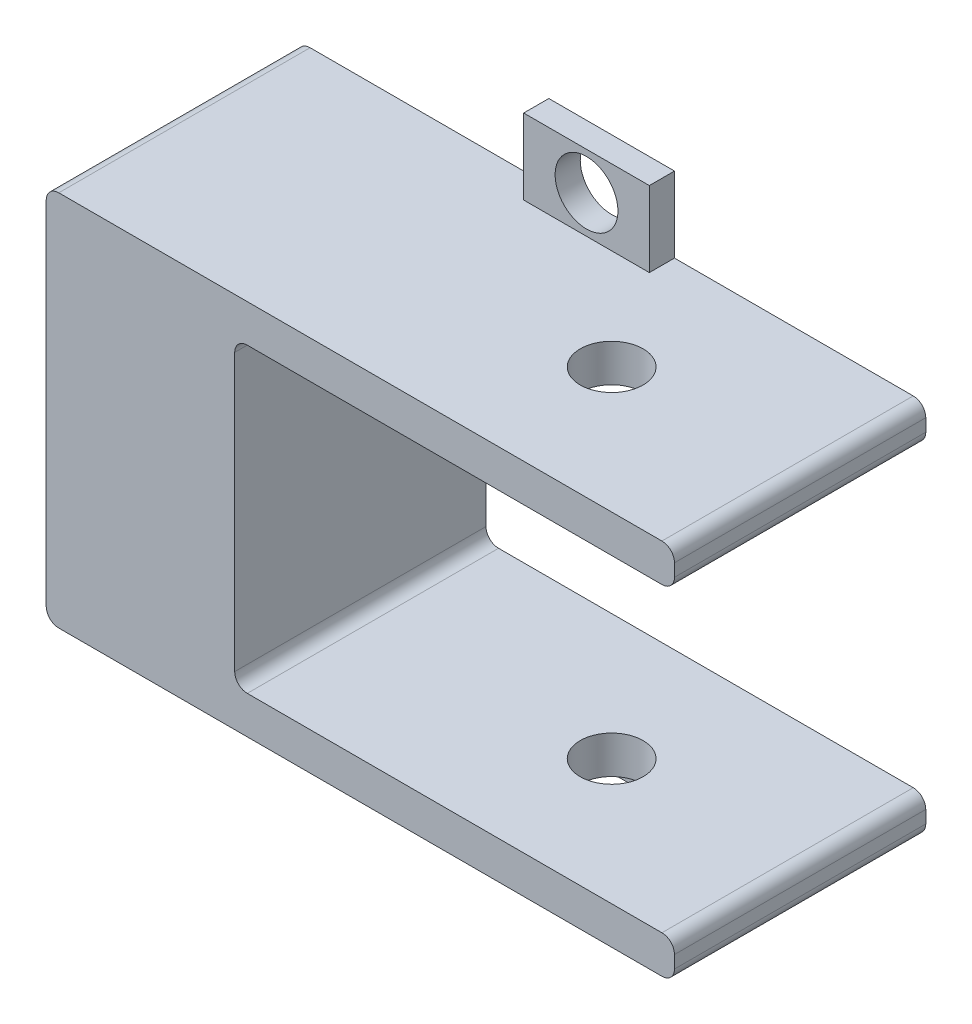
SolidWorks part; units mm, degrees
ref_plane "Front Plane" through (0, 0, 0) normal (0, 0, 1) x (1, 0, 0)
ref_plane "Top Plane" through (0, 0, 0) normal (0, 1, 0) x (1, 0, 0)
ref_plane "Right Plane" through (0, 0, 0) normal (1, 0, 0) x (0, 0, -1)
sketch "Sketch1" plane through (0, 0, 0) normal (0, 0, 1) x (1, 0, 0)
  line L1 (0, 0) -> (63.5, 0)
  line L2 (0, 0) -> (0, 38.1)
  line L3 (0, 38.1) -> (63.5, 38.1)
  line L4 (63.5, 0) -> (63.5, 38.1)
  dimension "D1" = 38.1
  dimension "D2" = 63.5
extrude "Boss-Extrude1" add sketch "Sketch1" along normal blind 25.4
sketch "Sketch3" plane through (0, 0, 0) normal (0, 0, -1) x (-1, 0, 0)
  line L0 (-63.5, 0) -> (-63.5, 38.1) construction
  line L1 (-63.5, 34.29) -> (-19.05, 34.29)
  line L2 (-63.5, 34.29) -> (-63.5, 3.81)
  line L3 (-63.5, 3.81) -> (-19.05, 3.81)
  line L4 (-19.05, 34.29) -> (-19.05, 3.81)
  line L9 (0, 0) -> (-63.5, 0) construction
  line L10 (-63.5, 38.1) -> (0, 38.1) construction
  dimension "D1" = 3.81
  dimension "D2" = 3.81
  dimension "D3" = 44.45
extrude "Cut-Extrude1" cut sketch "Sketch3" against normal blind 38.1
sketch "Sketch5" plane through (0, 0, 0) normal (0, -1, 0) x (1, 0, 0)
  line L0 (0, 0) -> (63.5, 0) construction
  circle A0 centre (44.45, 12.7) radius 3.175
  dimension "D1" = 6.35
  dimension "D2" = 12.7
  dimension "D3" = 19.05
extrude "Cut-Extrude2" cut sketch "Sketch5" against normal blind 76.2
fillet "Fillet3" radius 1.27 8 edges at (0, 38.1, 12.7) (0, 0, 12.7) (19.05, 3.81, 12.7) (19.05, 34.29, 12.7) (63.5, 3.81, 12.7) (63.5, 38.1, 12.7) (63.5, 34.29, 12.7) (63.5, 0, 12.7)
sketch "Sketch6" plane through (0, 38.1, 0) normal (0, 1, 0) x (1, 0, 0)
  line L5 (1.27, -25.4) -> (62.23, -25.4) construction
  line L6 (1.27, -22.86) -> (25.4, -22.86) construction
  line L7 (25.4, -25.4) -> (38.1, -25.4)
  line L8 (25.4, -25.4) -> (25.4, -22.86)
  line L9 (25.4, -22.86) -> (38.1, -22.86)
  line L10 (38.1, -25.4) -> (38.1, -22.86)
  line L11 (1.27, 0) -> (1.27, -25.4) construction
  line L12 (1.27, 0) -> (62.23, 0) construction
  dimension "D1" = 2.54
  dimension "D2" = 12.7
  dimension "D3" = 24.13
  dimension "D4" = 60.96
sketch "Sketch7" plane through (0, 0, 0) normal (0, -1, 0) x (1, 0, 0)
  line L0 (62.23, 22.86) -> (38.1, 22.86) construction
  line L1 (62.23, 0) -> (62.23, 25.4) construction
  line L2 (1.27, 25.4) -> (62.23, 25.4) construction
  line L3 (38.1, 22.86) -> (25.4, 22.86)
  line L4 (38.1, 22.86) -> (38.1, 25.4)
  line L5 (38.1, 25.4) -> (25.4, 25.4)
  line L6 (25.4, 22.86) -> (25.4, 25.4)
  dimension "D1" = 24.13
  dimension "D2" = 12.7
  dimension "D3" = 2.54
sketch "Sketch10" plane through (0, 0, 0) normal (0, -1, 0) x (1, 0, 0)
  line L0 (62.23, 2.54) -> (38.1, 2.54) construction
  line L1 (62.23, 0) -> (62.23, 25.4) construction
  line L2 (1.27, 0) -> (62.23, 0) construction
  line L3 (38.1, 2.54) -> (25.4, 2.54)
  line L4 (38.1, 2.54) -> (38.1, 0)
  line L5 (38.1, 0) -> (25.4, 0)
  line L6 (25.4, 2.54) -> (25.4, 0)
  dimension "D1" = 24.13
  dimension "D2" = 12.7
  dimension "D3" = 2.54
extrude "Boss-Extrude4" add sketch "Sketch10" along normal blind 7.62
sketch "Sketch11" plane through (0, 38.1, 0) normal (0, 1, 0) x (1, 0, 0)
  line L0 (1.27, -2.54) -> (25.4, -2.54) construction
  line L1 (1.27, 0) -> (1.27, -25.4) construction
  line L2 (62.23, 0) -> (1.27, 0) construction
  line L3 (25.4, -2.54) -> (38.1, -2.54)
  line L4 (25.4, -2.54) -> (25.4, 0)
  line L5 (25.4, 0) -> (38.1, 0)
  line L6 (38.1, -2.54) -> (38.1, 0)
  dimension "D1" = 24.13
  dimension "D2" = 12.7
  dimension "D3" = 2.54
extrude "Boss-Extrude5" add sketch "Sketch11" along normal blind 7.62
sketch "Sketch12" plane through (0, 0, 2.54) normal (0, 0, 1) x (1, 0, 0)
  line L0 (25.4, 41.91) -> (38.1, 41.91) construction
  line L1 (25.4, 45.72) -> (25.4, 38.1) construction
  line L2 (38.1, 45.72) -> (38.1, 38.1) construction
  line L3 (25.4, -3.81) -> (38.1, -3.81) construction
  line L4 (25.4, -7.62) -> (25.4, 0) construction
  line L5 (38.1, -7.62) -> (38.1, 0) construction
  circle A0 centre (31.75, 41.91) radius 3.175
  circle A1 centre (31.75, -3.81) radius 3.175
  dimension "D1" = 6.35
  dimension "D2" = 6.35
extrude "Cut-Extrude5" cut sketch "Sketch12" against normal up to next
